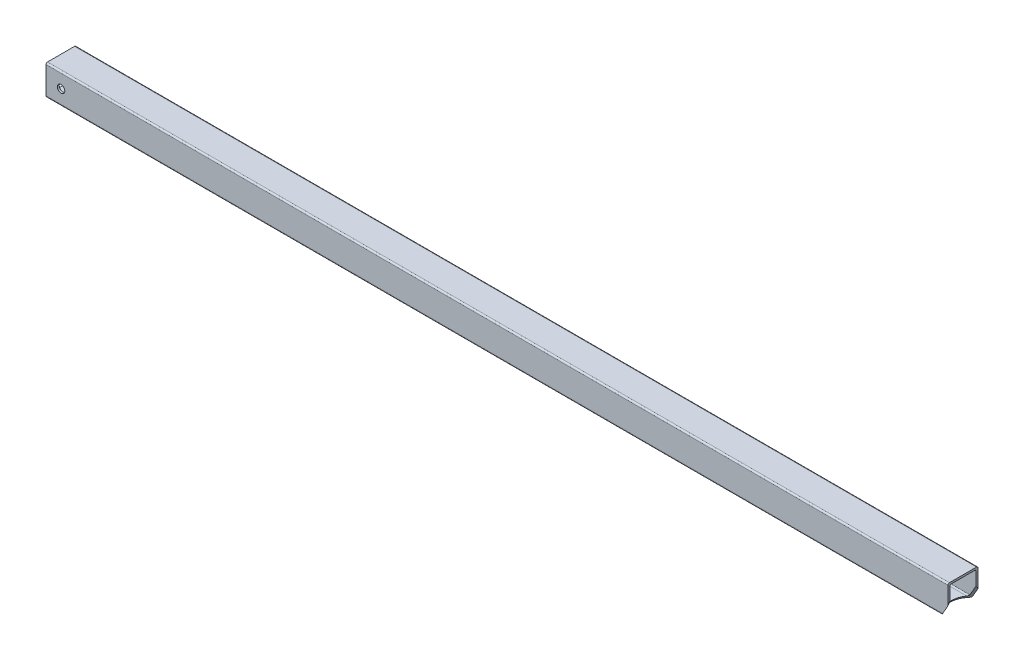
SolidWorks part; units mm, degrees
ref_plane "Front" through (0, 0, 0) normal (0, 0, 1) x (1, 0, 0)
ref_plane "Top" through (0, 0, 0) normal (0, 1, 0) x (1, 0, 0)
ref_plane "Right" through (0, 0, 0) normal (1, 0, 0) x (0, 0, -1)
sketch "Sketch1" plane through (0, 0, 0) normal (1, 0, 0) x (0, 0, -1)
  line L0 (-11.049, 0) -> (-12.7, 0) construction
  line L1 (11.43, -12.7) -> (-11.43, -12.7) construction
  line L2 (12.7, -11.43) -> (12.7, 11.43) construction
  line L3 (11.43, 12.7) -> (-11.43, 12.7) construction
  line L4 (-12.7, -11.43) -> (-12.7, 11.43) construction
  line L5 (12.7, -12.7) -> (-12.7, 12.7) construction
  line L6 (12.7, 12.7) -> (-12.7, -12.7) construction
  line L7 (9.9441, 11.049) -> (-9.9441, 11.049) construction
  line L8 (11.049, 9.9441) -> (11.049, -9.9441) construction
  line L9 (9.9441, -11.049) -> (-9.9441, -11.049) construction
  line L10 (-11.049, 9.9441) -> (-11.049, -9.9441) construction
  line L11 (11.049, 11.049) -> (-11.049, -11.049) construction
  line L12 (11.049, -11.049) -> (-11.049, 11.049) construction
  line L13 (0, -11.049) -> (0, -12.7) construction
  line L14 (11.049, -9.9441) -> (11.049, -12.7) construction
  line L15 (11.049, 0) -> (12.7, 0) construction
  line L16 (11.049, -12.7) -> (12.7, -12.7) construction
  arc A0 (-9.9441, -11.049) -> (-11.049, -9.9441) centre (-9.9441, -9.9441) cw construction
  arc A1 (11.049, -9.9441) -> (9.9441, -11.049) centre (9.9441, -9.9441) cw construction
  arc A2 (9.9441, 11.049) -> (11.049, 9.9441) centre (9.9441, 9.9441) cw construction
  arc A3 (-9.9441, 11.049) -> (-11.049, 9.9441) centre (-9.9441, 9.9441) ccw construction
  arc A4 (11.43, -12.7) -> (12.7, -11.43) centre (11.43, -11.43) ccw construction
  arc A5 (12.7, 11.43) -> (11.43, 12.7) centre (11.43, 11.43) ccw construction
  arc A6 (-11.43, 12.7) -> (-12.7, 11.43) centre (-11.43, 11.43) ccw construction
  arc A7 (-11.43, -12.7) -> (-12.7, -11.43) centre (-11.43, -11.43) cw construction
  point P0 (0, 0)
  point P6 (0, 0)
  dimension "D2" = 1.1049
  dimension "D3" = 1.27
  dimension "Outside Width" = 25.4
  dimension "Ouside Height" = 25.4
  dimension "Inside Height" = 22.098
  dimension "Wall Thickness" = 1.651
sketch "Sketch2" plane through (0, 0, 0) normal (0, 0, 1) x (1, 0, 0)
  line L0 (-381, 0) -> (381, 0) construction
  point P3 (-357.251, 0)
  point P4 (357.251, 0)
  dimension "Length" = 762
  dimension "D1" = 23.749
  dimension "D2" = 23.749
sketch "Sketch4" plane through (0, 0, 0) normal (1, 0, 0) x (0, 0, -1)
  line L8 (12.7, -11.43) -> (12.7, 11.43)
  line L9 (11.43, 12.7) -> (-11.43, 12.7)
  line L10 (-12.7, -11.43) -> (-12.7, 11.43)
  line L11 (11.43, -12.7) -> (-11.43, -12.7)
  line L12 (11.049, 9.9441) -> (11.049, -9.9441)
  line L13 (9.9441, -11.049) -> (-9.9441, -11.049)
  line L14 (-11.049, 9.9441) -> (-11.049, -9.9441)
  line L15 (9.9441, 11.049) -> (-9.9441, 11.049)
  arc A8 (12.7, 11.43) -> (11.43, 12.7) centre (11.43, 11.43) ccw
  arc A9 (-11.43, 12.7) -> (-12.7, 11.43) centre (-11.43, 11.43) ccw
  arc A10 (-12.7, -11.43) -> (-11.43, -12.7) centre (-11.43, -11.43) ccw
  arc A11 (11.43, -12.7) -> (12.7, -11.43) centre (11.43, -11.43) ccw
  arc A12 (9.9441, -11.049) -> (11.049, -9.9441) centre (9.9441, -9.9441) ccw
  arc A13 (-11.049, -9.9441) -> (-9.9441, -11.049) centre (-9.9441, -9.9441) ccw
  arc A14 (-9.9441, 11.049) -> (-11.049, 9.9441) centre (-9.9441, 9.9441) ccw
  arc A15 (11.049, 9.9441) -> (9.9441, 11.049) centre (9.9441, 9.9441) ccw
extrude "Boss-Extrude1" add sketch "Sketch4" along normal up to vertex (-381 mm away) and the other way up to vertex (-381 mm away) up to point (-381, 0, 0) other way up to point (381, 0, 0)
sketch "Sketch5" plane through (0, 0, 12.7) normal (0, 0, 1) x (1, 0, 0)
  line L0 (381, 12.7) -> (-381, 12.7) construction
  line L1 (-381, 11.43) -> (-381, -11.43) construction
  circle A0 centre (-368.3, 0) radius 3.175
  dimension "D1" = 12.7
  dimension "D2" = 12.7
  dimension "D3" = 6.35
extrude "Cut-Extrude1" cut sketch "Sketch5" against normal through all
ref_plane "Plane1" through (100.7493, 174.5028, 0) normal (0.5, 0.866, 0) x (0, 0, 1)
sketch "Sketch6" plane through (100.7493, 174.5028, 0) normal (0.5, 0.866, 0) x (0, 0, 1)
  line L0 (0, -664.5198) -> (0, 49335.4802) construction
  line L1 (9.9441, 335.4802) -> (-9.9441, 335.4802) construction
  line L3 (-1029.9563, 345.998) -> (48970.0437, 345.998) construction
  circle A4 centre (0, 345.998) radius 19.05
  circle A5 centre (0, 345.998) radius 19.05 construction
  point P3 (0, 0)
  point P7 (0, 335.4802)
extrude "Cut-Extrude2" cut sketch "Sketch6" against normal through all
equation "\"D3@Sketch1\"=\"Outside Width@Sketch1\"*.05"
equation "\"D2@Sketch1\" = \"Inside Height@Sketch1\" * .05"
equation "\"D1@Sketch2\"=\"Outside Width@Sketch1\"-\"Wall Thickness@Sketch1\""
equation "\"D2@Sketch2\"=\"D1@Sketch2\""
